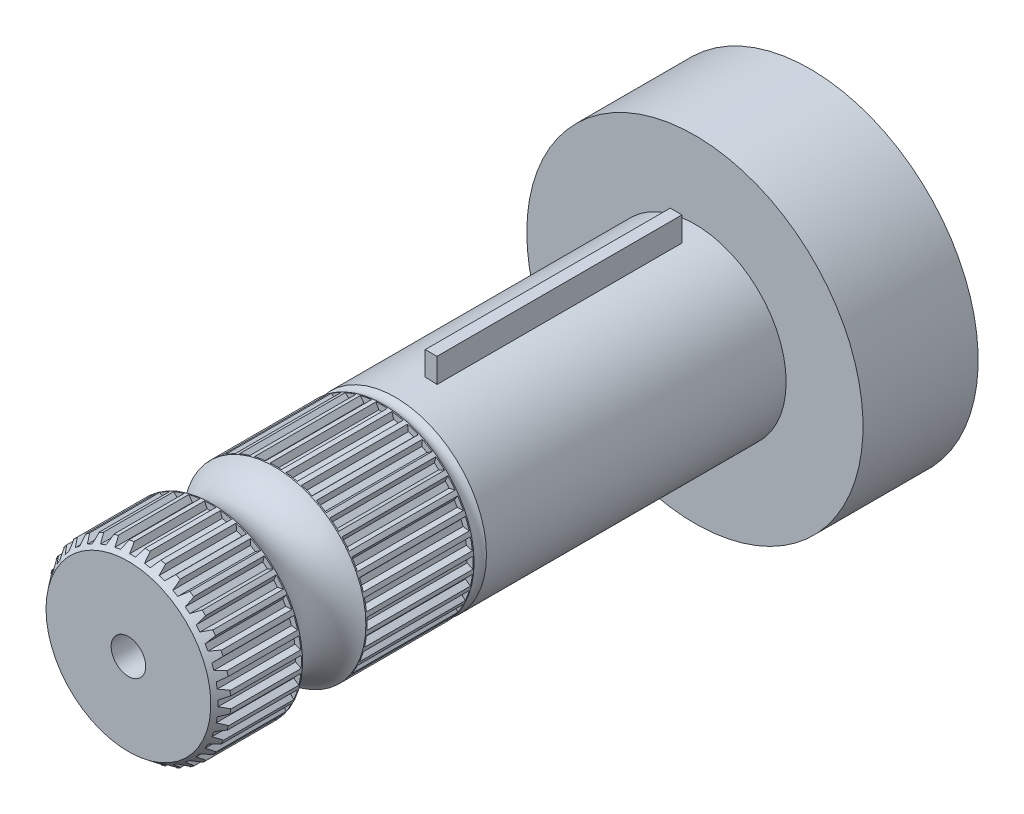
SolidWorks part; units mm, degrees
ref_plane "Front Plane" through (0, 0, 0) normal (0, 0, 1) x (1, 0, 0)
ref_plane "Top Plane" through (0, 0, 0) normal (0, 1, 0) x (1, 0, 0)
ref_plane "Right Plane" through (0, 0, 0) normal (1, 0, 0) x (0, 0, -1)
sketch "Sketch1" plane through (0, 0, 0) normal (0, 0, 1) x (1, 0, 0)
  circle A0 centre (0, 0) radius 7.9225
  dimension "D1" = 15.845
extrude "Boss-Extrude1" add sketch "Sketch1" along normal blind 49.2 and the other way blind 10
sketch "Sketch8" plane through (0, 0, 49.2) normal (0, 0, 1) x (1, 0, 0)
  circle A0 centre (0, 0) radius 1.5
  dimension "D1" = 3
sketch "Sketch9" plane through (0, 0, -10) normal (0, 0, -1) x (-1, 0, 0)
  circle A0 centre (0, 0) radius 14.6
  dimension "D1" = 29.2
extrude "Boss-Extrude2" add sketch "Sketch9" against normal blind 10
sketch "Sketch5" plane through (0, 0, -10) normal (0, 0, -1) x (-1, 0, 0)
  line L1 (0.25, 7.4225) -> (-0.25, 7.4225)
  line L2 (0.25, 7.4225) -> (0.75, 8.4225)
  line L3 (0.75, 8.4225) -> (-0.75, 8.4225)
  line L4 (-0.25, 7.4225) -> (-0.75, 8.4225)
  line L5 (0.25, 7.4225) -> (-0.75, 8.4225) construction
  line L6 (0.75, 8.4225) -> (-0.25, 7.4225) construction
  circle A1 centre (0, 0) radius 7.9225 construction
  point P0 (0, 7.6725)
  point P5 (0, 7.4225)
  point P7 (0, 8.4225)
  dimension "D1" = 0.5
  dimension "D2" = 0.5
  dimension "D3" = 1.5
  dimension "D4" = 0.5
extrude "Cut-Extrude1" cut sketch "Sketch5" along normal blind 7.9 from offset 60 offset against normal yes
pattern_circular "CirPattern1" count 36 over 360 about axis through (0, 0, -10) along (0, 0, 1) of "Cut-Extrude1"
sketch "Sketch11" plane through (0, 0, 0) normal (0, 1, 0) x (1, 0, 0)
  line L0 (7.9225, -42.1) -> (7.9225, 0) construction
  line L1 (0, 0) -> (0, -49.2) construction
  line L2 (7.9225, -36.5) -> (9.4418, -39.25)
  line L3 (9.4418, -39.25) -> (7.9225, -42)
  arc A0 (7.9225, -42) -> (7.9225, -36.5) centre (9.4418, -39.25) cw
  dimension "D3" = 6.3
  dimension "D1" = 0.1
  dimension "D2" = 5.5
revolve "Cut-Revolve1" cut sketch "Sketch11" angle 360 about axis through (0, 0, -10) along (0, 0, 1)
extrude "Cut-Extrude2" cut sketch "Sketch5<2>" along normal blind 9.2 from offset 46.4 offset against normal yes
sketch "Sketch5<2>" plane through (0, 0, -10) normal (0, 0, -1) x (-1, 0, 0) same geometry as "Sketch5"
pattern_circular "CirPattern2" count 36 over 360 about axis through (0, 0, 0) along (0, 0, -1) of "Cut-Extrude2"
extrude "Cut-Extrude3" cut sketch "Sketch8" against normal blind 5
sketch "Sketch12" plane through (0, 0, 0) normal (0, 1, 0) x (1, 0, 0)
  line L0 (7.9225, -27.2) -> (7.9225, 0) construction
  line L1 (7.9225, -26.0257) -> (8.4597, -26.5628)
  line L2 (8.4597, -26.5628) -> (7.9225, -27.1)
  line L3 (0, 0) -> (0, 10) construction
  arc A0 (7.9225, -27.1) -> (7.9225, -26.0257) centre (8.4597, -26.5628) cw
  dimension "D2" = 7.7
  dimension "D1" = 0.1
revolve "Cut-Revolve2" cut sketch "Sketch12" angle 360 about axis through (0, 0, 0) along (0, 0, -1)
sketch "Sketch13" plane through (0, 0, 0) normal (1, 0, 0) x (0, 0, -1)
  line L0 (-49.2, 6.5531) -> (-49.2, 7.094) construction
  line L1 (-42.1, 7.9072) -> (-49.2, 7.9072) construction
  line L2 (-49.2, 7.1572) -> (-50.1873, 8.6218)
  line L3 (-50.1873, 8.6218) -> (-48.2, 7.9072)
  spline S0 degree 1 poles (-49.2, 7.1572) (-48.2, 7.9072) knots 0 0 1 1
  dimension "D1" = 1
  dimension "D2" = 0.75
revolve "Cut-Revolve3" cut sketch "Sketch13" angle 360 about axis through (0, 0, -10) along (0, 0, 1)
sketch "Sketch14" plane through (0, 0, 0) normal (0, 1, 0) x (1, 0, 0)
  line L0 (-0.1951, -1.9499) -> (-0.1951, -23.2252)
  line L1 (-0.1951, -23.2252) -> (0.8227, -23.2252)
  line L2 (0.8227, -23.2252) -> (0.8227, -1.9499)
  line L3 (0.8227, -1.9499) -> (-0.1951, -1.9499)
extrude "Boss-Extrude3" add sketch "Sketch14" along normal blind 10
